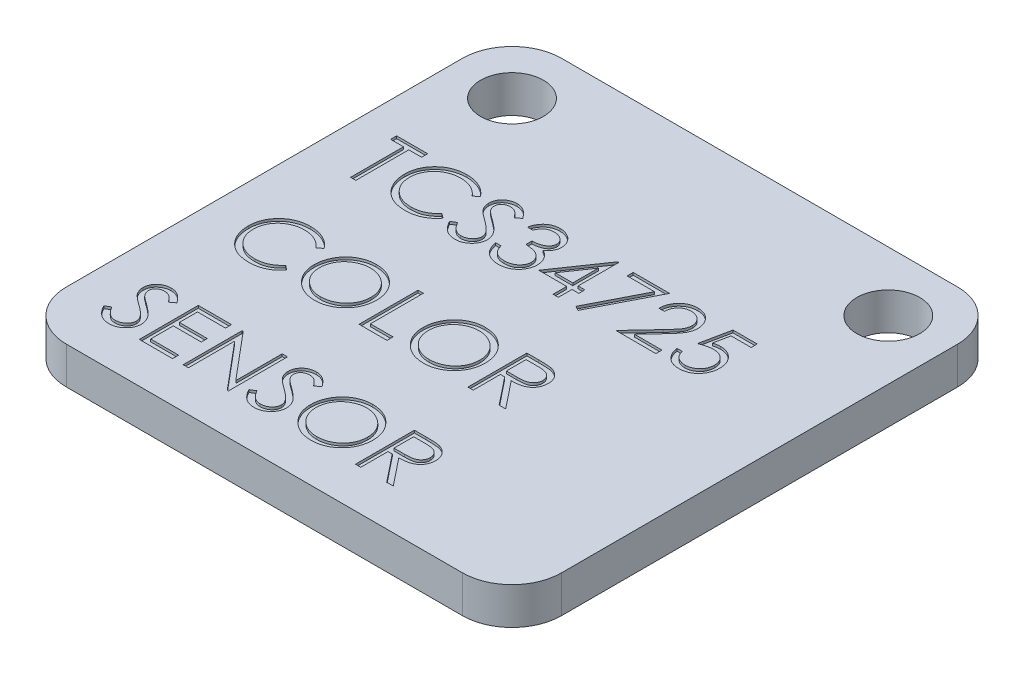
SolidWorks part; units mm, degrees
ref_plane "Front Plane" through (0, 0, 0) normal (0, 0, 1) x (1, 0, 0)
ref_plane "Top Plane" through (0, 0, 0) normal (0, 1, 0) x (1, 0, 0)
ref_plane "Right Plane" through (0, 0, 0) normal (1, 0, 0) x (0, 0, -1)
sketch "Sketch1" plane through (0, 0, 0) normal (0, 1, 0) x (1, 0, 0)
  line L0 (-7.6, 7.6) -> (7.6, 7.6) construction
  line L1 (-8, -10) -> (8, -10)
  line L2 (-10, -8) -> (-10, 8)
  line L3 (-8, 10) -> (8, 10)
  line L4 (10, -8) -> (10, 8)
  line L5 (-10, -10) -> (10, 10) construction
  line L6 (-10, 10) -> (10, -10) construction
  circle A0 centre (-7.6, 7.6) radius 1.27
  circle A1 centre (7.6, 7.6) radius 1.27
  arc A2 (-8, 10) -> (-10, 8) centre (-8, 8) ccw
  arc A3 (10, 8) -> (8, 10) centre (8, 8) ccw
  arc A4 (-8, -10) -> (-10, -8) centre (-8, -8) cw
  arc A5 (10, -8) -> (8, -10) centre (8, -8) cw
  point P0 (0, 0)
  dimension "D4" = 2.54
  dimension "D5" = 2.54
  dimension "D6" = 2
  dimension "D7" = 2
  dimension "D8" = 2
  dimension "D9" = 2
  dimension "D1" = 20
  dimension "D2" = 20
  dimension "D3" = 15.2
extrude "Boss-Extrude1" add sketch "Sketch1" along normal blind 1.5
sketch "Sketch2" plane through (0, 1.5, 0) normal (0, 1, 0) x (1, 0, 0)
  text T0 "TCS34725\r\nCOLOR\r\nSENSOR" font "Century Gothic" height in points 9
  point P1 (-8.8137, 1.8548)
  point P2 (-8.8973, -2.1895)
  point P3 (-8.8973, -4.0024)
  point P4 (-8.8416, -3.8351)
  point P5 (-8.6184, 2.4126)
  point P6 (-8.6463, 1.5759)
extrude "Cut-Extrude1" cut sketch "Sketch2" against normal blind 0.1
